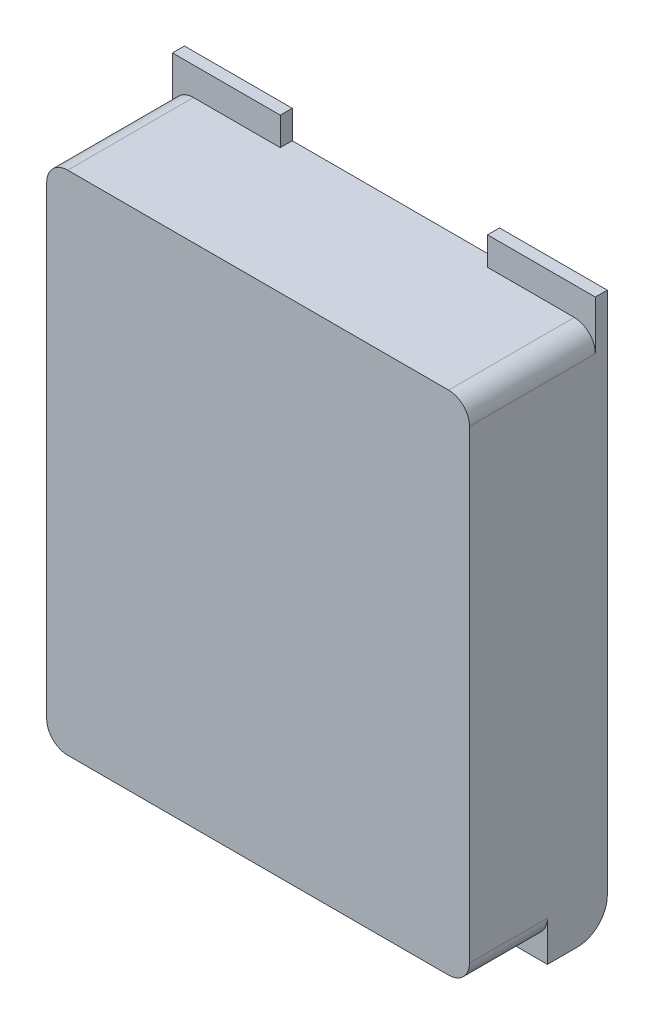
SolidWorks part; units mm, degrees
ref_plane "前视基准面" through (0, 0, 0) normal (0, 0, 1) x (1, 0, 0)
ref_plane "上视基准面" through (0, 0, 0) normal (0, 1, 0) x (1, 0, 0)
ref_plane "右视基准面" through (0, 0, 0) normal (1, 0, 0) x (0, 0, -1)
other "Configuration Table"
sketch "草图1" plane through (0, 0, 0) normal (0, 0, 1) x (1, 0, 0)
  line L0 (74, 195) -> (74, 110) construction
  line L1 (73.8, 110.2) -> (3.2, 110.2)
  line L2 (73.8, 110.2) -> (73.8, 194.8)
  line L3 (73.8, 194.8) -> (3.2, 194.8)
  line L4 (3.2, 110.2) -> (3.2, 194.8)
  line L5 (3, 110) -> (3, 195) construction
  line L6 (74, 110) -> (3, 110) construction
  line L7 (3, 195) -> (74, 195) construction
  dimension "D1" = 0.2
  dimension "D2" = 0.2
  dimension "D3" = 0.2
  dimension "D4" = 0.2
extrude "凸台-拉伸1" add sketch "草图1" against normal up to surface (23 mm away)
sketch "草图2" plane through (0, 0, -23) normal (0, 0, -1) x (-1, 0, 0)
  line L0 (-82.5, 200) -> (4.5, 200) construction
  line L1 (-3.2, 194.8) -> (-21.2, 194.8)
  line L2 (-3.2, 194.8) -> (-3.2, 199.5)
  line L3 (-3.2, 199.5) -> (-21.2, 199.5)
  line L4 (-21.2, 194.8) -> (-21.2, 199.5)
  line L5 (-38.5, 195) -> (-38.5, 212.554) construction
  line L6 (-73.5, 195) -> (-3.5, 195) construction
  line L8 (-73.8, 199.5) -> (-55.8, 199.5)
  line L9 (-73.8, 194.8) -> (-55.8, 194.8)
  line L10 (-73.8, 194.8) -> (-73.8, 199.5)
  line L11 (-55.8, 194.8) -> (-55.8, 199.5)
  dimension "D1" = 18
  dimension "D2" = 0.5
extrude "凸台-拉伸2" add sketch "草图2" against normal blind 2
sketch "草图3" plane through (0, 0, -23) normal (0, 0, -1) x (-1, 0, 0)
  line L0 (-74, 107) -> (-3, 107) construction
  line L1 (-3.2, 110.2) -> (-73.8, 110.2)
  line L2 (-3.2, 110.2) -> (-3.2, 107)
  line L3 (-3.2, 107) -> (-73.8, 107)
  line L4 (-73.8, 110.2) -> (-73.8, 107)
  line L5 (-73.8, 110.2) -> (-73.8, 199.5) construction
extrude "凸台-拉伸3" add sketch "草图3" against normal up to surface (10 mm away)
sketch "草图4" plane through (0, 194.8, 0) normal (0, 1, 0) x (1, 0, 0)
  line L1 (73.8, 21) -> (73.8, 23) construction
  line L2 (73.8, 13) -> (3.2, 13) construction
  circle A0 centre (60.8, 25) radius 11
  point P4 (61.1991, 25.1044)
  dimension "D1" = 22
  dimension "D2" = 2
  dimension "D3" = 1
extrude "切除-拉伸1" cut sketch "草图4" against normal through all from offset 2 offset against normal yes
sketch "草图5" plane through (0, 107, 0) normal (0, -1, 0) x (1, 0, 0)
  arc A0 (71.6167, -23) -> (49.9833, -23) centre (60.8, -25) ccw construction
  arc A1 (71.6167, -23) -> (49.9833, -23) centre (60.8, -25) ccw
extrude "拉伸-薄壁1" add sketch "草图5" against normal blind 2 thin thin type one direction reverse wall 2
other "删除面1" face at (70.6333, 108, -23.1818) face at (50.9667, 108, -23.1818) and patch yes
sketch "草图6" plane through (3.2, 0, 0) normal (-1, 0, 0) x (0, 0, 1)
  line L0 (-23, 107) -> (-15, 107)
  line L1 (-13, 107) -> (-23, 107) construction
  line L2 (-15, 107) -> (-15, 112.2)
  line L3 (-15, 112.2) -> (-2, 112.2)
  line L4 (-2, 112.2) -> (-2, 192.8)
  line L5 (-2, 192.8) -> (-23, 192.8)
  line L6 (-23, 199.5) -> (-23, 107) construction
  line L7 (-23, 192.8) -> (-23, 107)
  line L8 (-13, 110.2) -> (-13, 107) construction
  line L9 (-13, 110.2) -> (0, 110.2) construction
  line L10 (0, 194.8) -> (0, 110.2) construction
  line L11 (-21, 194.8) -> (0, 194.8) construction
  dimension "D1" = 2
  dimension "D2" = 2
  dimension "D3" = 2
  dimension "D4" = 2
extrude "切除-拉伸2" cut sketch "草图6" against normal blind 43 and the other way blind 1 from offset 2 offset against normal yes
sketch "草图7" plane through (4.2, 0, 0) normal (1, 0, 0) x (0, 0, -1)
  line L6 (23, 107) -> (23, 192.8)
  line L7 (23, 192.8) -> (2, 192.8)
  line L8 (2, 192.8) -> (2, 112.2)
  line L9 (2, 112.2) -> (15, 112.2)
  line L10 (15, 112.2) -> (15, 107)
  line L11 (15, 107) -> (23, 107)
  line L12 (23, 107) -> (23, 192.8)
  line L13 (23, 192.8) -> (2, 192.8)
  line L14 (2, 192.8) -> (2, 112.2)
  line L15 (2, 112.2) -> (15, 112.2)
  line L16 (15, 112.2) -> (15, 107)
  line L17 (15, 107) -> (23, 107)
  dimension "D1" = 0
extrude "凸台-拉伸4" add sketch "草图7" along normal blind 2 from offset 24
fillet "圆角1" radius 5 4 edges at (71.6875, 107, -23) (50.1125, 107, -23) (29.2, 107, -23) (3.7, 107, -23)
fillet "圆角2" radius 3.5 4 edges at (73.8, 110.2, -6.5) (3.2, 110.2, -6.5) (3.2, 194.8, -10.5) (73.8, 194.8, -10.5)
fillet "圆角3" radius 3.5 16 edges at (39.2, 112.2, -2) (48.2, 152.5, -2) (39.2, 192.8, -2) (30.2, 152.5, -2) (4.2, 152.5, -2) (16.2, 112.2, -2) (28.2, 152.5, -2) (16.2, 192.8, -2) (30.2, 112.2, -8.5) (48.2, 112.2, -8.5) (30.2, 192.8, -12.5) (48.2, 192.8, -12.5) (4.2, 192.8, -12.5) (4.2, 112.2, -8.5) (28.2, 112.2, -8.5) (28.2, 192.8, -12.5)
